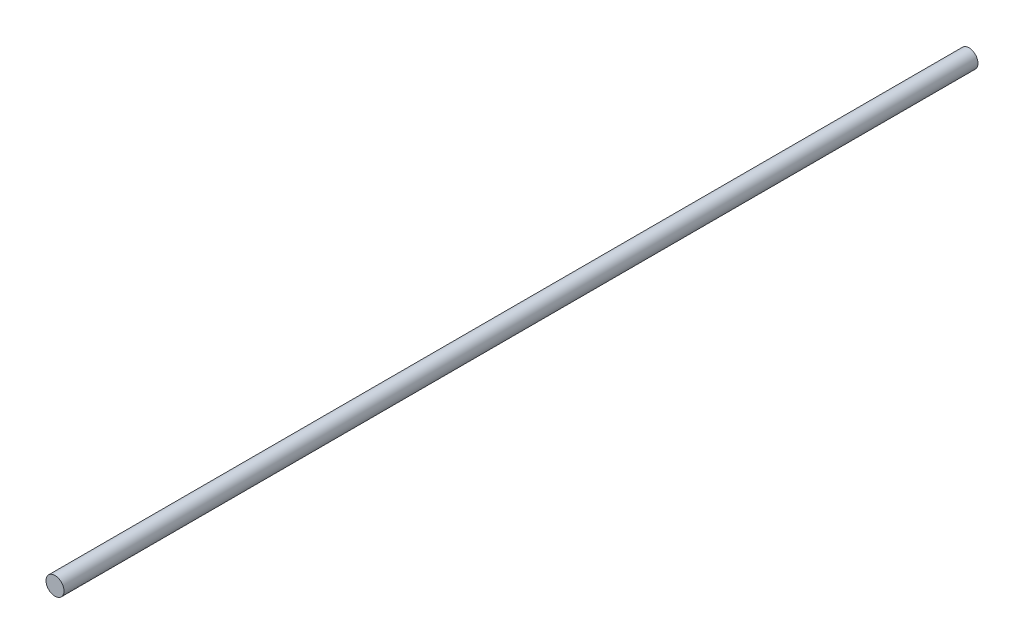
SolidWorks part; units mm, degrees
note: '?' marks a value the reader was unsure of.
material "AISI 316 Stainless Steel Sheet (SS)"
ref_plane "Front (1)" through (0, 0, 0) normal (0, 0, 1) x (1, 0, 0)
ref_plane "Top (2)" through (0, 0, 0) normal (0, 1, 0) x (1, 0, 0)
ref_plane "Right (3)" through (0, 0, 0) normal (1, 0, 0) x (0, 0, -1)
ref_axis "X Axis" through (13.5064, 0, 0) along (-1, 0, 0)?
ref_axis "Y Axis" through (0, 12.3593, 0) along (0, -1, 0)?
ref_axis "Z Axis" through (0, 0, 14.1119) along (0, 0, -1)?
sketch "Sketch2" plane through (0, 0, 0) normal (1, 0, 0) x (0, 0, -1)
  line L0 (-72.9, 0) -> (0, 0) construction
  line L1 (-72.9, 0) -> (332.9, 0)
  line L2 (-72.9, 0) -> (-72.9, 4)
  line L3 (-72.9, 4) -> (332.9, 4)
  line L4 (332.9, 0) -> (332.9, 4)
  dimension "D1" = 8
  dimension "D2" = 405.8
  dimension "D3" = 11.3
  dimension "D4" = 11.3
revolve "Revolve1" add sketch "Sketch2" angle 360 about L0
cosmetic thread "Cosmetic Thread2" parameters "D2"=6.891
